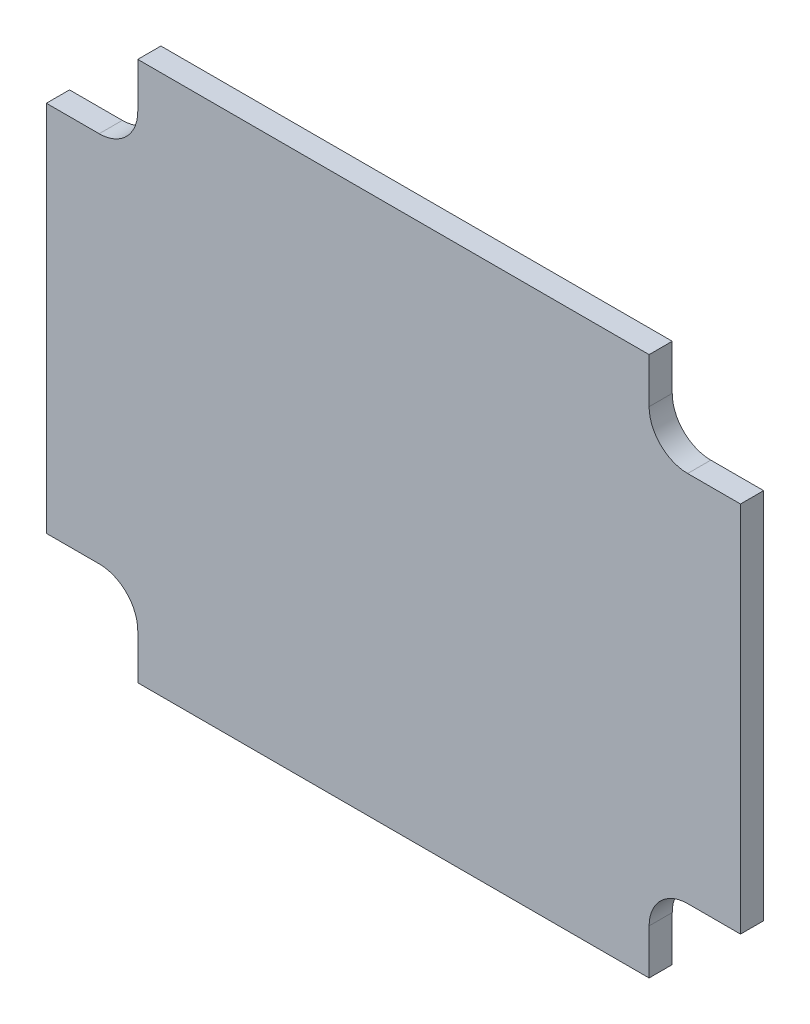
SolidWorks part; units mm, degrees
ref_plane "前视基准面" through (0, 0, 0) normal (0, 0, 1) x (1, 0, 0)
ref_plane "上视基准面" through (0, 0, 0) normal (0, 1, 0) x (1, 0, 0)
ref_plane "右视基准面" through (0, 0, 0) normal (1, 0, 0) x (0, 0, -1)
sketch "草图3" plane through (0, 0, 0) normal (0, 0, 1) x (1, 0, 0)
  line L0 (-0.0737, 34.1637) -> (-0.0737, -35.8363) construction
  line L1 (33.0763, 23.3137) -> (44.9263, 23.3137)
  line L2 (44.9263, -24.9863) -> (44.9263, 23.3137)
  line L3 (33.0763, -24.9863) -> (44.9263, -24.9863)
  line L4 (33.0763, -24.9863) -> (33.0763, 23.3137)
  line L5 (-45.0737, -0.8363) -> (44.9263, -0.8363) construction
  line L6 (-33.2237, -35.8363) -> (33.0763, -35.8363)
  line L7 (-33.2237, 23.3137) -> (33.0763, 23.3137)
  line L8 (-33.2237, 23.3137) -> (-33.2237, 34.1637)
  line L9 (-33.2237, 34.1637) -> (33.0763, 34.1637)
  line L10 (33.0763, 23.3137) -> (33.0763, 34.1637)
  line L11 (33.0763, -24.9863) -> (33.0763, -35.8363)
  line L12 (-33.2237, -24.9863) -> (33.0763, -24.9863)
  line L13 (-45.0737, 34.1637) -> (44.9263, 34.1637)
  line L14 (-45.0737, 34.1637) -> (-45.0737, -35.8363)
  line L15 (-45.0737, -35.8363) -> (44.9263, -35.8363)
  line L16 (44.9263, 34.1637) -> (44.9263, -35.8363)
  line L17 (-33.2237, -24.9863) -> (-45.0737, -24.9863)
  line L18 (-33.2237, -24.9863) -> (-33.2237, 23.3137)
  line L19 (-33.2237, 23.3137) -> (-45.0737, 23.3137)
  line L20 (-45.0737, -24.9863) -> (-45.0737, 23.3137)
  line L21 (-33.2237, -24.9863) -> (-45.0737, 23.3137) construction
  line L22 (-33.2237, 23.3137) -> (-45.0737, -24.9863) construction
  line L23 (-33.2237, -24.9863) -> (-33.2237, -35.8363)
  line L26 (-45.0737, -35.8363) -> (44.9263, -35.8363)
  line L32 (44.9263, 34.1637) -> (-45.0737, 34.1637)
  point P0 (-39.1487, -0.8363)
  point P23 (0, 0)
  dimension "D1" = 48.3
  dimension "D2" = 70
  dimension "D3" = 90
  dimension "D4" = 66.3
extrude "凸台-拉伸1" add sketch "草图3" along normal blind 3 contours L18 L12 L4 L7 | L18 L19 L14 L17 | L12 L23 L6 L11 | L7 L10 L9 L8 | L4 L3 L2 L1 region at (39.0013, -0.8363, 0) region at (-0.0737, -0.8363, 0) region at (-0.0737, 28.7387, 0) region at (-0.0737, -30.4113, 0) region at (-39.1487, -0.8363, 0)
fillet "圆角1" radius 5 4 edges at (-33.2237, -24.9863, 1.5) (33.0763, -24.9863, 1.5) (33.0763, 23.3137, 1.5) (-33.2237, 23.3137, 1.5)
